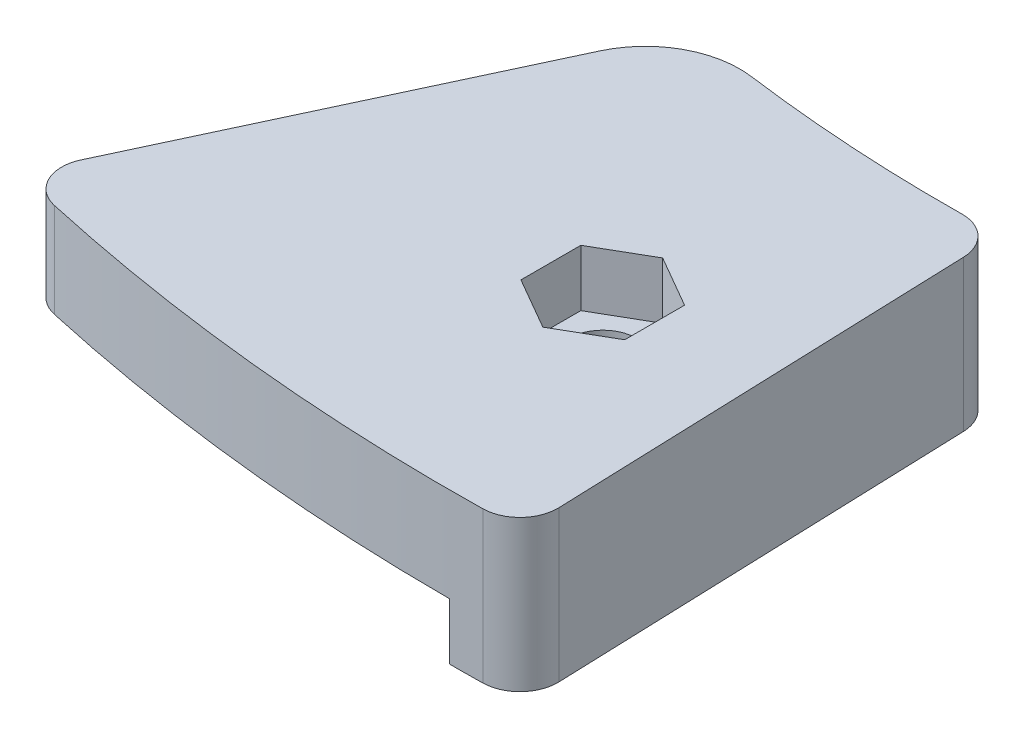
SolidWorks part; units mm, degrees
ref_plane "Plano frontal" through (0, 0, 0) normal (0, 0, 1) x (1, 0, 0)
ref_plane "Plano superior" through (0, 0, 0) normal (0, 1, 0) x (1, 0, 0)
ref_plane "Plano direito" through (0, 0, 0) normal (1, 0, 0) x (0, 0, -1)
sketch "Esboço6" plane through (0, 0, 0) normal (0, 1, 0) x (1, 0, 0)
  line L0 (0, 0) -> (0, -82.26) construction
  line L1 (0, -82.26) -> (0, -108.5)
  line L2 (0, 0) -> (-14.5819, -80.9572) construction
  line L3 (-14.5819, -80.9572) -> (-25.9562, -105.3495)
  arc A0 (-25.9562, -105.3495) -> (0, -108.5) centre (0, 0) ccw
  arc A1 (-14.5819, -80.9572) -> (0, -82.26) centre (0, 0) ccw
  point P3 (-5.9617, -26.8473)
  point P9 (-15.5092, -80.7847)
  dimension "D2" = 164.52
  dimension "D3" = 217
  dimension "D1" = 25
  dimension "D4" = 14.64
extrude "Ressalto-extrusão4" add sketch "Esboço6" along normal blind 5
sketch "Esboço8" plane through (0, 5, 0) normal (0, 1, 0) x (1, 0, 0)
  line L0 (-5, -95.38) -> (0, -95.38) construction
  line L3 (0, -108.5) -> (0, -82.26) construction
  circle A0 centre (-5, -95.38) radius 1.8
  dimension "D1" = 3.6
  dimension "D2" = 5
extrude "Corte-extrusão3" cut sketch "Esboço8" against normal through all
sketch "Esboço7" plane through (0, 5, 0) normal (0, 1, 0) x (1, 0, 0)
  line L0 (0, 0) -> (0, -82.26)
  line L1 (0, -82.26) -> (0, -108.5)
  line L2 (0, 0) -> (2.8708, -82.2099)
  line L3 (2.8708, -82.2099) -> (3.7866, -108.4339)
  arc A0 (0, -82.26) -> (2.8708, -82.2099) centre (0, 0) ccw
  arc A1 (0, -108.5) -> (3.7866, -108.4339) centre (0, 0) ccw
  point P10 (0, 0)
  line M8 (0, -108.5) -> (0, -82.26)
  dimension "D1" = 2
extrude "Ressalto-extrusão5" add sketch "Esboço7" against normal blind 8 contours A1 L3 A0 M8 region at (1.675, 5, 95.9621)
sketch "Esboço9" plane through (0, 5, 0) normal (0, 1, 0) x (1, 0, 0)
  line L0 (-7.75, -93.7923) -> (-7.75, -96.9677)
  line L1 (-7.75, -96.9677) -> (-5, -98.5554)
  line L2 (-5, -98.5554) -> (-2.25, -96.9677)
  line L3 (-2.25, -96.9677) -> (-2.25, -93.7923)
  line L4 (-2.25, -93.7923) -> (-5, -92.2046)
  line L5 (-5, -92.2046) -> (-7.75, -93.7923)
  circle A0 centre (-5, -95.38) radius 3.1754 construction
  dimension "D1" = 5.5
extrude "Corte-extrusão4" cut sketch "Esboço9" against normal blind 3
fillet "Filete1" radius 5 1 edges at (-14.5819, 2.5, 80.9572)
fillet "Filete2" radius 2 4 edges at (-25.9562, 2.5, 105.3495) (2.8708, 1, 82.2099) (3.7866, 1, 108.4339) (0, -1.5, 82.26)
